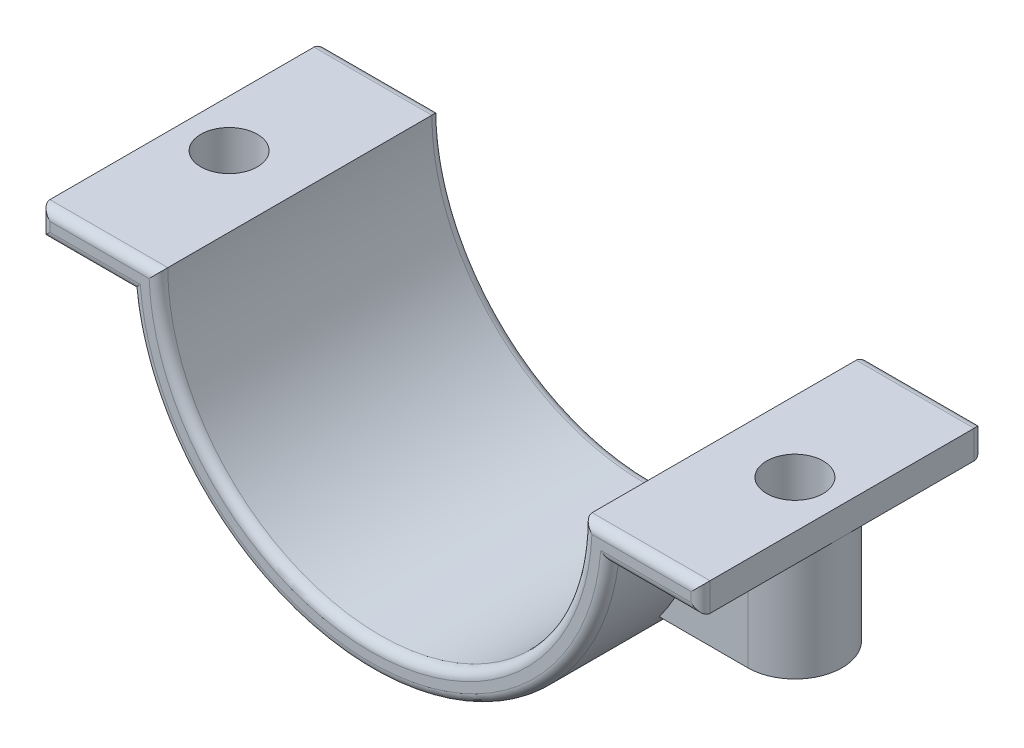
SolidWorks part; units mm, degrees
ref_plane "Front Plane" through (0, 0, 0) normal (0, 0, 1) x (1, 0, 0)
ref_plane "Top Plane" through (0, 0, 0) normal (0, 1, 0) x (1, 0, 0)
ref_plane "Right Plane" through (0, 0, 0) normal (1, 0, 0) x (0, 0, -1)
sketch "Sketch2" plane through (0, 0, 0) normal (0, 0, 1) x (1, 0, 0)
  line L0 (-35, 0) -> (-22.5, 0)
  line L1 (22.5, 0) -> (35, 0)
  line L2 (-35, -3) -> (-25.3229, -3)
  line L3 (25.3229, -3) -> (35, -3)
  line L4 (-35, 0) -> (-35, -3)
  line L5 (35, 0) -> (35, -3)
  arc A0 (-22.5, 0) -> (22.5, 0) centre (0, 0) ccw
  arc A1 (-25.3229, -3) -> (25.3229, -3) centre (0, 0) ccw
  point P6 (0, 0)
  dimension "D1" = 22.5
  dimension "D2" = 35
  dimension "D3" = 3
extrude "Boss-Extrude1" add sketch "Sketch2" along normal mid plane 30
sketch "Sketch4" plane through (0, -3, 0) normal (0, -1, 0) x (1, 0, 0)
  line L0 (35, 15) -> (35, -15) construction
  line L1 (18, 5) -> (30, 5)
  line L2 (18, 5) -> (18, -5)
  line L3 (18, -5) -> (30, -5)
  line L4 (30, 5) -> (30, -5)
  line L5 (18, 5) -> (30, -5) construction
  line L6 (18, -5) -> (30, 5) construction
  circle A0 centre (30, 0) radius 5
  circle A1 centre (30, 0) radius 3
  point P0 (24, 0)
  line M9 (25.3229, 15) -> (25.3229, -15)
  dimension "D1" = 10
  dimension "D3" = 6
  dimension "D2" = 12
extrude "Boss-Extrude2" add sketch "Sketch4" against normal up to body from offset 12 contours A1 L4 A0 | A1 L4 A0 M9 | A0 L1 L2 L3 M9 | A0 L3 M9 | A0 L1 M9 region at (21.6241, -3, 0) region at (26.4044, -3, 4.1253) region at (33.4565, -3, 3.4565) region at (29.8896, -3, 4) region at (26.4044, -3, -4.1253)
fillet "Fillet1" radius 1 16 edges at (-30.1615, -3, -15) (0, -25.5, -15) (30.1615, -3, -15) (35, -1.5, -15) (28.75, 0, -15) (0, -22.5, -15) (-28.75, 0, -15) (-35, -1.5, -15) (-28.75, 0, 15) (0, -22.5, 15) (28.75, 0, 15) (35, -1.5, 15) (30.1615, -3, 15) (0, -25.5, 15) (-30.1615, -3, 15) (-35, -1.5, 15)
extrude "Cut-Extrude1" cut sketch "Sketch4<4>" against normal through all contours A1
sketch "Sketch4<4>" plane through (0, -3, 0) normal (0, -1, 0) x (1, 0, 0) same geometry as "Sketch4"
mirror "Mirror1" about plane through (0, 0, 0) normal (1, 0, 0) of "Boss-Extrude2"
sketch "Sketch5" plane through (0, -15, 0) normal (0, -1, 0) x (1, 0, 0)
  circle A0 centre (-30, 0) radius 3
extrude "Cut-Extrude2" cut sketch "Sketch5" against normal through all
